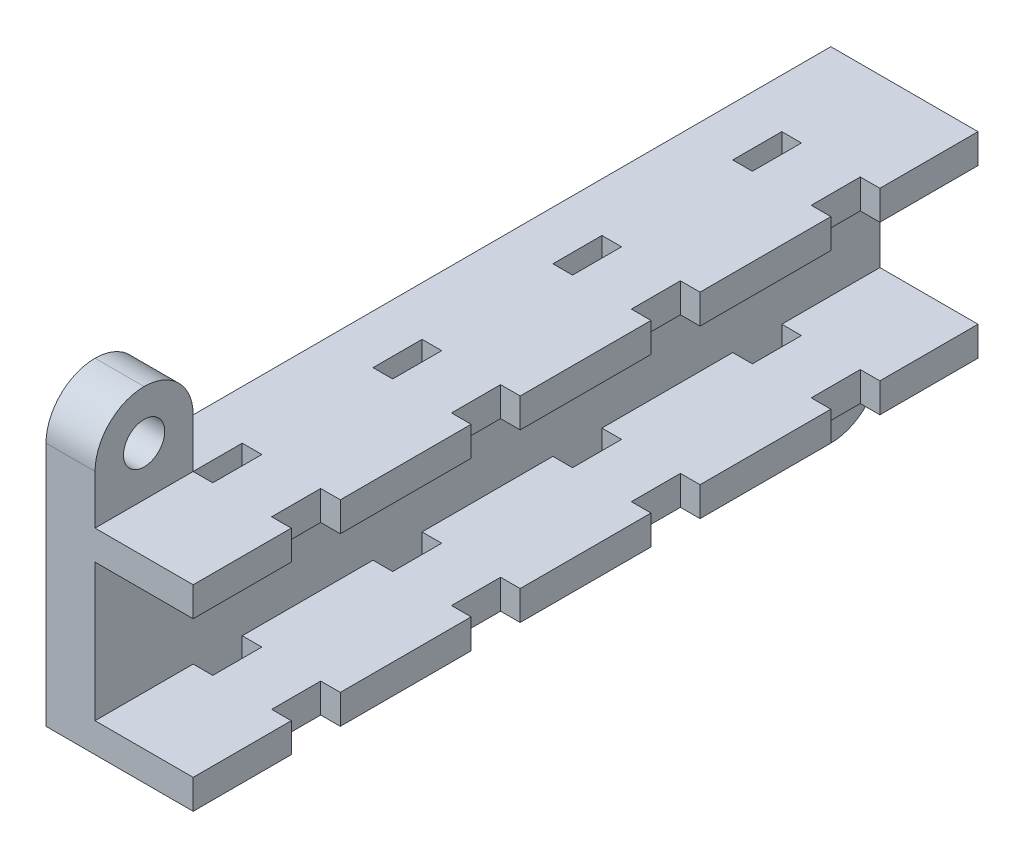
SolidWorks part; units mm, degrees
ref_plane "Front Plane" through (0, 0, 0) normal (0, 0, 1) x (1, 0, 0)
ref_plane "Top Plane" through (0, 0, 0) normal (0, 1, 0) x (1, 0, 0)
ref_plane "Right Plane" through (0, 0, 0) normal (1, 0, 0) x (0, 0, -1)
sketch "Sketch1" plane through (0, 0, 0) normal (1, 0, 0) x (0, 0, -1)
  line L0 (0, 10) -> (0, -10) construction
  line L1 (-40, 10) -> (40, 10)
  line L2 (-40, 10) -> (-40, -10)
  line L3 (-40, -10) -> (40, -10)
  line L4 (40, 10) -> (40, -10)
  line L5 (-40, 10) -> (40, -10) construction
  line L6 (-40, -10) -> (40, 10) construction
  line L7 (-40, 10) -> (-30, 10)
  line L8 (-40, 10) -> (-40, 20)
  line L9 (-40, 20) -> (-30, 20)
  line L10 (-30, 10) -> (-30, 20)
  line L11 (-35, 20) -> (-35, 10) construction
  line L12 (40, -10) -> (30, -10)
  line L13 (40, -10) -> (40, -20)
  line L14 (40, -20) -> (30, -20)
  line L15 (30, -10) -> (30, -20)
  line L16 (35, -20) -> (35, -10) construction
  circle A0 centre (-35, 15) radius 2.1
  circle A1 centre (35, -15) radius 2.1
  point P0 (0, 0)
  dimension "D5" = 4.2
  dimension "D1" = 80
  dimension "D2" = 20
  dimension "D3" = 10
  dimension "D4" = 10
extrude "Boss-Extrude1" add sketch "Sketch1" along normal blind 5 contours L4 L1 L2 L3 | L1 L10 L9 L8 A0 | L3 L15 L14 L13 A1 region at (0, 15, 39.8586) region at (0, 0, 0) region at (0, -10.1414, -35)
sketch "Sketch2" plane through (0, 0, 40) normal (0, 0, 1) x (1, 0, 0)
  line L0 (15, 0) -> (5, 0) construction
  line L1 (5, -10) -> (15, -10)
  line L2 (5, -10) -> (5, 10)
  line L3 (5, 10) -> (15, 10)
  line L4 (15, -10) -> (15, 10)
  line L5 (15, 10) -> (5, 10)
  line L6 (15, 10) -> (15, 7)
  line L7 (15, 7) -> (5, 7)
  line L8 (5, 10) -> (5, 7)
  line L9 (15, -7) -> (5, -7)
  line L10 (5, -10) -> (5, -7)
  line L11 (15, -10) -> (5, -10)
  line L12 (15, -10) -> (15, -7)
  point P10 (10, 10)
  point P11 (10, 7)
  line M12 (5, -10) -> (5, 20)
  dimension "D1" = 10
  dimension "D2" = 3
extrude "Boss-Extrude2" add sketch "Sketch2" against normal up to surface (80 mm away) contours L7 L4 L3 L2 | L4 L9 L1 M12 region at (10, -8.5, 40) region at (10, 8.5, 40) up to face at (2.5, -5, -40)
fillet "Fillet1" radius 5 4 edges at (2.5, 20, 30) (2.5, 20, 40) (2.5, -20, -40) (2.5, -20, -30)
sketch "Sketch3" plane through (0, -10, 0) normal (0, -1, 0) x (1, 0, 0)
  line L0 (5, -6.6667) -> (5, -11.6667)
  line L5 (10, 40) -> (10, -40) construction
  line L6 (15, 40) -> (5, 40)
  line L7 (15, 40) -> (15, -40)
  line L8 (15, -40) -> (5, -40)
  line L9 (5, 40) -> (5, -40)
  line L10 (5, -6.6667) -> (7, -6.6667)
  line L11 (7, -6.6667) -> (7, -11.6667)
  line L12 (5, -25) -> (7, -25)
  line L13 (5, -25) -> (5, -30)
  line L14 (5, -30) -> (7, -30)
  line L15 (7, -25) -> (7, -30)
  line L16 (5, -11.6667) -> (7, -11.6667)
  line L17 (5, 11.6667) -> (5, 6.6667)
  line L18 (5, 11.6667) -> (7, 11.6667)
  line L19 (7, 11.6667) -> (7, 6.6667)
  line L20 (5, 6.6667) -> (7, 6.6667)
  line L21 (5, 30) -> (5, 25)
  line L22 (5, 30) -> (7, 30)
  line L23 (7, 30) -> (7, 25)
  line L24 (5, 25) -> (7, 25)
  line L25 (15, 25) -> (13, 25)
  line L26 (13, 30) -> (13, 25)
  line L27 (15, 30) -> (13, 30)
  line L28 (15, 30) -> (15, 25)
  line L29 (15, 6.6667) -> (13, 6.6667)
  line L30 (13, 11.6667) -> (13, 6.6667)
  line L31 (15, 11.6667) -> (13, 11.6667)
  line L32 (15, 11.6667) -> (15, 6.6667)
  line L33 (15, -11.6667) -> (13, -11.6667)
  line L34 (13, -25) -> (13, -30)
  line L35 (15, -30) -> (13, -30)
  line L36 (15, -25) -> (15, -30)
  line L37 (15, -25) -> (13, -25)
  line L38 (13, -6.6667) -> (13, -11.6667)
  line L39 (15, -6.6667) -> (13, -6.6667)
  line L40 (15, -6.6667) -> (15, -11.6667)
  dimension "D1" = 2
  dimension "D2" = 5
  dimension "D4" = 10
  dimension "D3" = 4
extrude "Cut-Extrude1" cut sketch "Sketch3" against normal through all contours L9 L24 L23 L22 | L9 L20 L19 L18 | L0 L16 L11 L10 | L15 L12 L9 L14 | L25 L26 L27 L28 | L29 L30 L31 L32 | L33 L38 L39 L40 | L34 L35 L36 L37 region at (6, -10, -9.1667) region at (6, -10, 9.1667) region at (6, -10, -27.5) region at (6, -10, 27.5)
